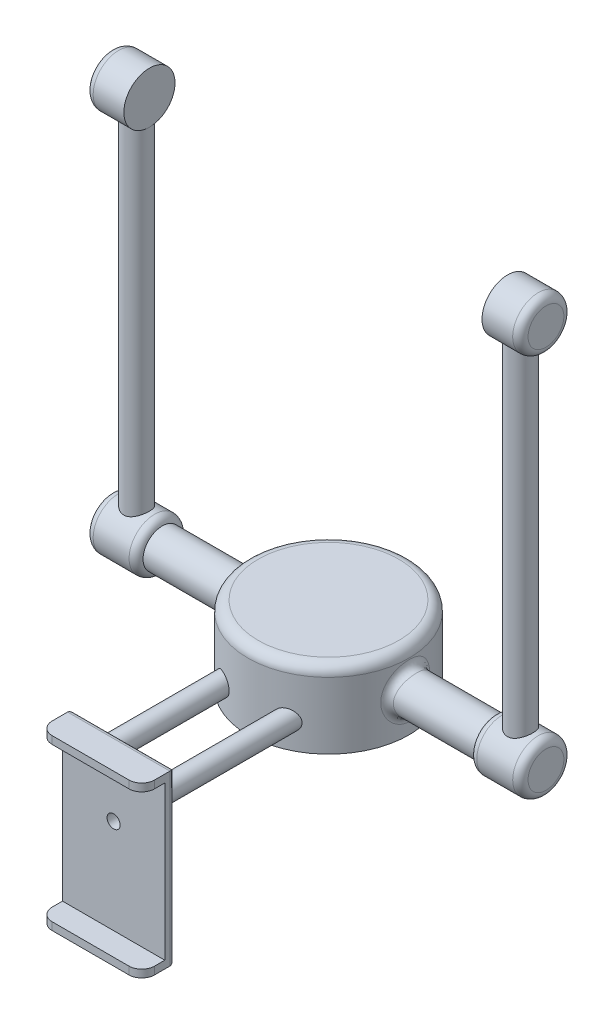
SolidWorks part; units mm, degrees
material "Polyester Resin"
ref_plane "Front Plane" through (0, 0, 0) normal (0, 0, 1) x (1, 0, 0)
ref_plane "Top Plane" through (0, 0, 0) normal (0, 1, 0) x (1, 0, 0)
ref_plane "Right Plane" through (0, 0, 0) normal (1, 0, 0) x (0, 0, -1)
sketch "Sketch1" plane through (0, 0, 0) normal (0, 1, 0) x (1, 0, 0)
  circle A0 centre (0, 0) radius 31.5
  dimension "D1" = 63
extrude "Boss-Extrude1" add sketch "Sketch1" along normal blind 30
sketch "Sketch2" plane through (0, 0, 0) normal (1, 0, 0) x (0, 0, -1)
  line L0 (0, 0) -> (0, 30) construction
  line L1 (31.5, 30) -> (-31.5, 30) construction
  circle A0 centre (0, 15) radius 7.5
  dimension "D1" = 15
extrude "Boss-Extrude2" add sketch "Sketch2" along normal blind 65
sketch "Sketch3" plane through (65, 0, 0) normal (1, 0, 0) x (0, 0, -1)
  circle A0 centre (0, 15) radius 10
  dimension "D1" = 20
extrude "Boss-Extrude3" add sketch "Sketch3" along normal blind 20
ref_axis "Axis1" through (0, 15, 0) along (1, 0, 0)
ref_plane "Plane1" through (0, 15, 0) normal (0, -1, 0) x (1, 0, 0)
sketch "Sketch4" plane through (0, 15, 0) normal (0, -1, 0) x (1, 0, 0)
  line L0 (0, 0) -> (65, 0) construction
  line L2 (65, 10) -> (65, -10) construction
  circle A0 centre (75, 0) radius 5
  dimension "D1" = 10
  dimension "D2" = 10
extrude "Boss-Extrude4" add sketch "Sketch4" against normal blind 150
sketch "Sketch5" plane through (85, 0, 0) normal (1, 0, 0) x (0, 0, -1)
  line L0 (0, 165) -> (0, 15) construction
  line L1 (5, 165) -> (-5, 165) construction
  circle A0 centre (0, 165) radius 10
  dimension "D1" = 20
extrude "Boss-Extrude5" add sketch "Sketch5" against normal blind 15
fillet "Fillet1" radius 3 4 edges at (30.6305, 16.492, -7.3501) (65, 15, -10) (85, 15, -10) (85, 165, -10)
mirror "Mirror1" about plane through (0, 0, 0) normal (1, 0, 0) of "Boss-Extrude5", "Boss-Extrude2", "Fillet1", "Boss-Extrude4", "Boss-Extrude3"
fillet "Fillet2" radius 4 1 edges at (0, 30, 31.5)
sketch "Sketch7" plane through (0, 0, 0) normal (0, 0, 1) x (1, 0, 0)
  line L0 (0, 0) -> (0, 10) construction
  line L2 (-12.5, 10) -> (12.5, 10) construction
  circle A1 centre (-12.5, 10) radius 4
  circle A2 centre (12.5, 10) radius 4
  point P6 (0, 10)
  dimension "D1" = 25
  dimension "D2" = 8
  dimension "D3" = 8
  dimension "D4" = 10
extrude "Boss-Extrude6" add sketch "Sketch7" along normal blind 80
sketch "Sketch8" plane through (0, 0, 80) normal (0, 0, 1) x (1, 0, 0)
  line L0 (-12.5, 10) -> (12.5, 10) construction
  line L1 (-20, 20) -> (20, 20)
  line L6 (-20, 20) -> (-20, -40)
  line L7 (-20, -40) -> (20, -40)
  line L8 (20, 20) -> (20, -40)
  line L9 (-20, 20) -> (20, -40) construction
  line L10 (-20, -40) -> (20, 20) construction
  line L11 (0, 20) -> (0, 10) construction
  line L12 (0, 20) -> (0, -3) construction
  circle A4 centre (0, -3) radius 2.555
  point P0 (0, -10)
  dimension "D5" = 23
  dimension "D4" = 5.11
  dimension "D1" = 10
  dimension "D2" = 60
  dimension "D3" = 40
extrude "Boss-Extrude7" add sketch "Sketch8" along normal blind 4
sketch "Sketch10" plane through (0, 20, 0) normal (0, 1, 0) x (1, 0, 0)
  line L0 (-20, -84) -> (-20, -80) construction
  line L1 (20, -80) -> (-20, -80)
  line L2 (20, -80) -> (20, -93)
  line L3 (20, -93) -> (-20, -93)
  line L4 (-20, -80) -> (-20, -93)
  dimension "D1" = 13
extrude "Boss-Extrude8" add sketch "Sketch10" along normal blind 3
sketch "Sketch11" plane through (0, -40, 0) normal (0, -1, 0) x (1, 0, 0)
  line L0 (-20, 84) -> (-20, 80) construction
  line L1 (20, 80) -> (-20, 80)
  line L2 (20, 80) -> (20, 93)
  line L3 (20, 93) -> (-20, 93)
  line L4 (-20, 80) -> (-20, 93)
  dimension "D1" = 13
extrude "Boss-Extrude9" add sketch "Sketch11" along normal blind 3
fillet "Fillet3" radius 5 4 edges at (-20, -41.5, 93) (20, -41.5, 93) (-20, 21.5, 93) (20, 21.5, 93)
fillet "Fillet4" radius 2 4 edges at (-20, -10, 80) (20, -10, 80) (0, 23, 80) (0, -43, 80)
sketch "Sketch6" plane through (0, 0, 0) normal (0, -1, 0) x (1, 0, 0)
  circle A0 centre (0, 0) radius 29
  dimension "D1" = 58
extrude "Cut-Extrude1" cut sketch "Sketch6" against normal offset from surface (25 mm away) 5 up to face at (0, 30, 27.5)
chamfer "Chamfer1" distance 15 angle 45 1 edges at (0, 25, 29)
